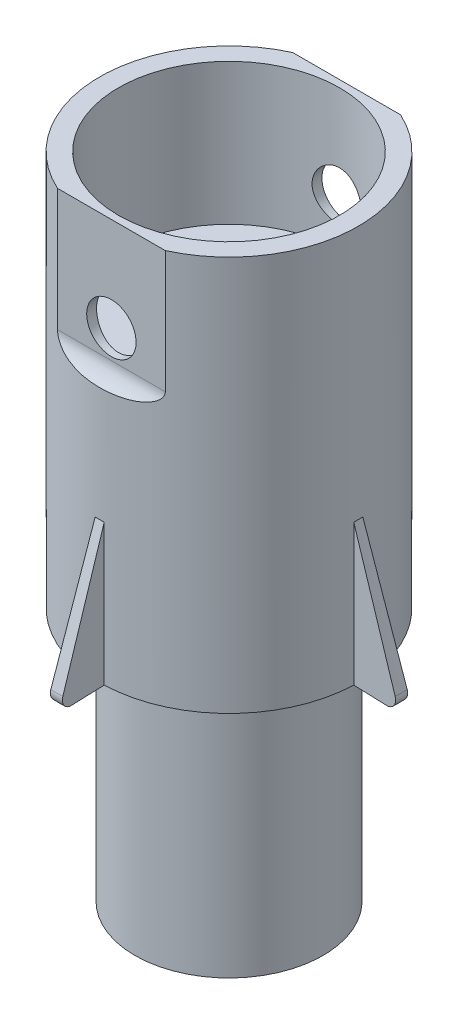
SolidWorks part; units mm, degrees
ref_plane "Front Plane" through (0, 0, 0) normal (0, 0, 1) x (1, 0, 0)
ref_plane "Top Plane" through (0, 0, 0) normal (0, 1, 0) x (1, 0, 0)
ref_plane "Right Plane" through (0, 0, 0) normal (1, 0, 0) x (0, 0, -1)
sketch "Sketch1" plane through (0, 0, 0) normal (0, 1, 0) x (1, 0, 0)
  circle A0 centre (0, 0) radius 10
  dimension "D1" = 20
extrude "Boss-Extrude1" add sketch "Sketch1" along normal blind 47
shell "Shell1" thickness 2 removed face at (0, 47, 10)
sketch "Sketch2" plane through (0, 47, 0) normal (0, 1, 0) x (1, 0, 0)
  line L1 (-4, -8.5) -> (4, -8.5)
  line L2 (-4, -8.5) -> (-4, 8.5)
  line L3 (-4, 8.5) -> (4, 8.5)
  line L4 (4, -8.5) -> (4, 8.5)
  line L5 (-4, -8.5) -> (4, 8.5) construction
  line L6 (-4, 8.5) -> (4, -8.5) construction
  point P0 (0, 0)
  dimension "D1" = 17
  dimension "D2" = 8
extrude "Cut-Extrude1" cut sketch "Sketch2" against normal up to surface (45 mm away) up to face at (0, 2, 8)
sketch "Sketch3" plane through (0, 0, 0) normal (0, 0, 1) x (1, 0, 0)
  line L1 (-10, 0) -> (10, 0) construction
  circle A0 centre (0, 7) radius 2.625
  dimension "D1" = 5.25
  dimension "D2" = 0
  dimension "D3" = 7
extrude "Cut-Extrude2" cut sketch "Sketch3" against normal through all
ref_plane "Plane1" through (0, 0, -10) normal (0, 0, 1) x (1, 0, 0)
sketch "Sketch4" plane through (0, 47, 0) normal (0, 1, 0) x (1, 0, 0)
  circle A1 centre (0, 0) radius 13.75
  dimension "D2" = 27.5
extrude "Boss-Extrude2" add sketch "Sketch4" along normal blind 22 contours A1
sketch "Sketch5" plane through (0, 47, 0) normal (0, -1, 0) x (1, 0, 0)
  circle A0 centre (0, 0) radius 12.75
  circle A1 centre (0, 0) radius 13.75
  dimension "D1" = 27.5
  dimension "D2" = 1
extrude "Boss-Extrude3" add sketch "Sketch5" along normal blind 20
fillet "Fillet1" radius 0.5 2 edges at (0, 47, -12.75) (0, 47, 10)
sketch "Sketch6" plane through (0, 0, 0) normal (1, 0, 0) x (0, 0, -1)
  line L1 (-4, 34.375) -> (4, 34.375)
  line L2 (-4, 34.375) -> (-4, 4.375)
  line L3 (-4, 4.375) -> (4, 4.375)
  line L4 (4, 34.375) -> (4, 4.375)
  line L5 (-4, 34.375) -> (4, 4.375) construction
  line L6 (-4, 4.375) -> (4, 34.375) construction
  point P0 (0, 19.375)
  point P5 (0, 4.375)
  dimension "D1" = 30
  dimension "D2" = 8
  dimension "D3" = 0
  dimension "D4" = 0
extrude "Cut-Extrude3" cut sketch "Sketch6" against normal blind 10
fillet "Fillet2" radius 4 2 edges at (-8.0467, 4.375, 4) (-8.0467, 4.375, -4)
sketch "Sketch7" plane through (0, 0, 0) normal (1, 0, 0) x (0, 0, -1)
  line L0 (13.75, 69) -> (-13.75, 69) construction
  line L1 (13.75, -20.1294) -> (13.75, 158.1294) construction
  line L2 (-13.75, 131.5178) -> (-13.75, 6.4822) construction
  line L3 (0, 49) -> (0, 55.2442) construction
  line L4 (-13.75, 69) -> (13.75, 69)
  line L5 (0, 84) -> (0, 69)
  spline S0 degree 3 poles (-13.75, 69) (-13.75, 75) (-4.7099, 84.055) (4.6396, 84.0947) (13.75, 75) (13.75, 69) knots 0 0 0 0 0.452706 0.552706 1 1 1 1
  dimension "D1" = 90
  dimension "D2" = 90
  dimension "D3" = 30
  dimension "D4" = 20
  dimension "D5" = 20
  dimension "D6" = 13.75
  dimension "D7" = 15
sketch "Sketch8" plane through (0, 0, 0) normal (1, 0, 0) x (0, 0, -1)
  line L0 (13.75, 27) -> (18.75, 27)
  line L1 (18.75, 27) -> (13.75, 42)
  line L2 (13.75, 27) -> (13.75, 69) construction
  line L3 (13.75, 42) -> (13.75, 27)
  dimension "D1" = 5
  dimension "D2" = 15
ref_axis "Axis1" through (0, 88.2, 0) along (0, -1, 0)
revolve "Revolve5" add sketch "Sketch8" angle 4 mid plane about axis through (0, 88.2, 0) along (0, -1, 0)
fillet "Fillet3" radius 1 1 edges at (0, 27, -18.75)
pattern_circular "CirPattern1" count 4 over 360 about axis through (0, 88.2, 0) along (0, -1, 0) of "Fillet3", "Revolve5"
sketch "Sketch9" plane through (0, 69, 0) normal (0, 1, 0) x (1, 0, 0)
  circle A0 centre (0, 0) radius 11.75
  circle A1 centre (0, 0) radius 13.75 construction
  dimension "D1" = 2
extrude "Cut-Extrude4" cut sketch "Sketch9" against normal blind 15
sketch "Sketch10" plane through (0, 0, 0) normal (0, 0, 1) x (1, 0, 0)
  line L0 (0, -0.922) -> (0, 35.3906) construction
  line L1 (13.75, 69) -> (-13.75, 69) construction
  circle A0 centre (0, 59) radius 2.625
  dimension "D2" = 5.25
  dimension "D1" = 10
extrude "Cut-Extrude6" cut sketch "Sketch10" against normal through all both and the other way through all contours A0
sketch "Sketch11" plane through (0, 69, 0) normal (0, 1, 0) x (1, 0, 0)
  line L0 (0, 0) -> (0, -3.3297) construction
  line L1 (-7.5, -12.5) -> (7.5, -12.5)
  line L2 (-7.5, -12.5) -> (-7.5, -14.5)
  line L3 (-7.5, -14.5) -> (7.5, -14.5)
  line L4 (7.5, -12.5) -> (7.5, -14.5)
  line L5 (-7.5, -12.5) -> (7.5, -14.5) construction
  line L6 (-7.5, -14.5) -> (7.5, -12.5) construction
  circle A0 centre (0, 0) radius 11.75 construction
  point P0 (0, -13.5)
  dimension "D1" = 12.5
  dimension "D2" = 15
  dimension "D3" = 2
extrude "Cut-Extrude7" cut sketch "Sketch11" against normal blind 15
mirror "Mirror1" about plane through (0, 0, 0) normal (0, 0, 1) of "Cut-Extrude7"
fillet "Fillet4" radius 2 2 edges at (0, 54, -12.5) (0, 54, 12.5)
